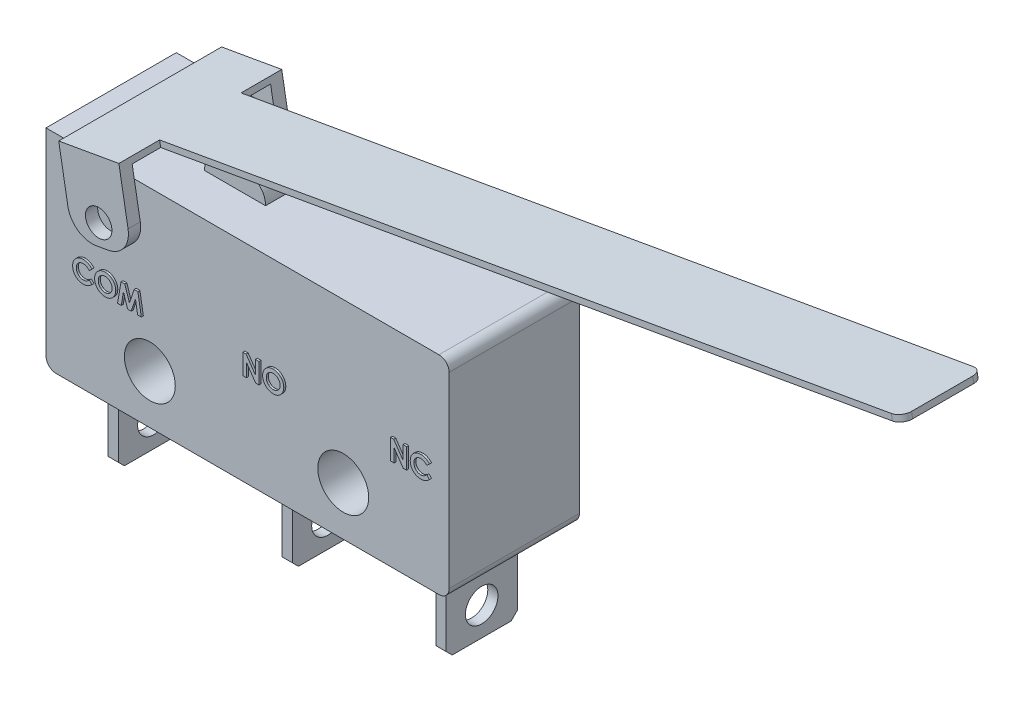
SolidWorks part; units mm, degrees
ref_plane "Front Plane" through (0, 0, 0) normal (0, 0, 1) x (1, 0, 0)
ref_plane "Top Plane" through (0, 0, 0) normal (0, 1, 0) x (1, 0, 0)
ref_plane "Right Plane" through (0, 0, 0) normal (1, 0, 0) x (0, 0, -1)
sketch "Sketch1" plane through (0, 0, 0) normal (0, 0, 1) x (1, 0, 0)
  line L0 (9.65, 5.1) -> (-9.65, 5.1)
  line L1 (10.15, 4.6) -> (10.15, -4.6)
  line L2 (9.65, -5.1) -> (-9.15, -5.1)
  line L3 (-9.65, 5.1) -> (-9.65, -4.6)
  circle A0 centre (-4.55, -2.7) radius 1.25
  circle A1 centre (4.95, -2.7) radius 1.25
  arc A2 (-9.15, -5.1) -> (-9.65, -4.6) centre (-9.15, -4.6) cw
  arc A3 (9.65, 5.1) -> (10.15, 4.6) centre (9.65, 4.6) cw
  arc A4 (10.15, -4.6) -> (9.65, -5.1) centre (9.65, -4.6) cw
  point P2 (0, 5.1)
  point P6 (10.15, 0)
  point P14 (-9.65, -5.1)
  point P17 (10.15, 5.1)
  dimension "D3" = 2.5
  dimension "D4" = 10.2
  dimension "D7" = 2.4
  dimension "D5" = 9.5
  dimension "D6" = 5.1
  dimension "D1" = 2.5
  dimension "D8" = 0.5
  dimension "D2" = 19.8
other "AlignGroup1"
other "AlignGroup2"
extrude "Boss-Extrude2" add sketch "Sketch1" along normal mid plane 6.4
sketch "Sketch2" plane through (0, -5.1, 0) normal (0, -1, 0) x (1, 0, 0)
  line L0 (-9.15, 3.2) -> (-9.15, -3.2) construction
  line L1 (-7.55, 1.75) -> (-8.05, 1.75)
  line L2 (-7.55, 1.75) -> (-7.55, -1.75)
  line L3 (-7.55, -1.75) -> (-8.05, -1.75)
  line L4 (-8.05, 1.75) -> (-8.05, -1.75)
  line L5 (-7.8, -1.75) -> (-7.8, 1.75) construction
  line L6 (-7.55, 0) -> (-8.05, 0) construction
  line L7 (-9.65, 3.2) -> (-9.65, -3.2) construction
  line L9 (1, -1.75) -> (0.5, -1.75)
  line L10 (1, -1.75) -> (1, 1.75)
  line L11 (1, 1.75) -> (0.5, 1.75)
  line L12 (0.5, -1.75) -> (0.5, 1.75)
  line L13 (0.75, 1.75) -> (0.75, -1.75) construction
  line L14 (1, 0) -> (0.5, 0) construction
  line L15 (8.05, -1.75) -> (8.55, -1.75)
  line L16 (8.05, -1.75) -> (8.05, 1.75)
  line L17 (8.05, 1.75) -> (8.55, 1.75)
  line L18 (8.55, -1.75) -> (8.55, 1.75)
  line L19 (8.3, 1.75) -> (8.3, -1.75) construction
  line L20 (8.05, 0) -> (8.55, 0) construction
  point P0 (-7.8, 0)
  point P4 (0.75, 0)
  point P11 (-9.15, 0)
  point P16 (8.3, 0)
  dimension "D1" = 0.5
  dimension "D2" = 3.5
  dimension "D3" = 1.6
  dimension "D4" = 0.5
  dimension "D5" = 3.5
  dimension "D6" = 3.5
  dimension "D7" = 0.5
  dimension "D8" = 8.8
  dimension "D9" = 7.3
extrude "Boss-Extrude3" add sketch "Sketch2" along normal blind 4
chamfer "Chamfer4" distance 0.3 angle 45 6 edges at (8.3, -9.1, 1.75) (8.3, -9.1, -1.75) (0.75, -9.1, 1.75) (0.75, -9.1, -1.75) (-7.8, -9.1, -1.75) (-7.8, -9.1, 1.75)
sketch "Sketch3" plane through (-8.05, 0, 0) normal (-1, 0, 0) x (0, 0, 1)
  line L0 (1.45, -9.1) -> (-1.45, -9.1) construction
  circle A0 centre (0, -7.7) radius 0.8
  point P4 (0, -9.1)
  dimension "D1" = 1.6
  dimension "D2" = 1.4
extrude "Cut-Extrude1" cut sketch "Sketch3" against normal through all
ref_plane "Plane1" through (-1.1631, 6.5965, 0) normal (0.1736, -0.9848, 0) x (0, 0, -1)
sketch "Sketch5" plane through (-1.1631, 6.5965, 0) normal (0.1736, -0.9848, 0) x (0, 0, -1)
  line L0 (-3.2, -8.6178) -> (3.2, -8.6178) construction
  line L1 (2, -7.1178) -> (-2, -7.1178)
  line L2 (2, -7.1178) -> (2, 32.3822)
  line L3 (1.5, 32.8822) -> (-1.5, 32.8822)
  line L4 (-2, -7.1178) -> (-2, 32.3822)
  line L5 (0, 0) -> (0, -8.6178) construction
  line L6 (2, -7.1178) -> (4, -7.1178)
  line L7 (4, -7.1178) -> (4, -4.1178)
  line L8 (2, -4.1178) -> (4, -4.1178)
  line L9 (2, -7.1178) -> (2, -4.1178)
  line L10 (-2, -7.1178) -> (-4, -7.1178)
  line L11 (-2, -7.1178) -> (-2, -4.1178)
  line L12 (-2, -4.1178) -> (-4, -4.1178)
  line L13 (-4, -7.1178) -> (-4, -4.1178)
  arc A0 (2, 32.3822) -> (1.5, 32.8822) centre (1.5, 32.3822) ccw
  arc A1 (-1.5, 32.8822) -> (-2, 32.3822) centre (-1.5, 32.3822) ccw
  point P12 (2, 32.8822)
  point P15 (-2, 32.8822)
  dimension "D3" = 0.5
  dimension "D1" = 4
  dimension "D2" = 40
  dimension "D4" = 1.5
  dimension "D6" = 2
  dimension "D7" = 3
sketch "Sketch7" plane through (0, 5.1, 0) normal (0, 1, 0) x (1, 0, 0)
  line L1 (-0.9455, 0.8808) -> (-3.9455, 0.8808)
  line L2 (-0.9455, 0.8808) -> (-0.9455, -1.1192)
  line L3 (-0.9455, -1.1192) -> (-3.9455, -1.1192)
  line L4 (-3.9455, 0.8808) -> (-3.9455, -1.1192)
  line L5 (-2.4455, -1.1192) -> (-2.4455, 0.8808) construction
  line L6 (-0.9455, -0.1192) -> (-3.9455, -0.1192) construction
  point P0 (-2.4455, -0.1192)
  dimension "D1" = 3
  dimension "D2" = 2
extrude "Boss-Extrude4" add sketch "Sketch7" along normal blind 1 contours L3 L4 L1 L2
fillet "Fillet5" radius 1 2 edges at (-0.9455, 6.1, 0.1192) (-3.9455, 6.1, 0.1192)
extrude "Boss-Extrude6" add sketch "Sketch5" against normal blind 0.3 separate body contours L3 A1 L4 L1 L2 A0 | L2 | L13 L10 L4 L12 region at (11.5102, 8.8311, 0) region at (-6.6956, 5.6209, -3) region at (-6.6956, 5.6209, 3)
sketch "Sketch9" plane through (-1.1631, 6.5965, 0) normal (0.1736, -0.9848, 0) x (0.9848, 0.1736, 0)
  line L0 (-4.1178, 4) -> (-7.1178, 4)
  line L1 (-4.1178, 4) -> (-4.1178, 3.4)
  line L2 (-7.1178, 4) -> (-7.1178, 3.4)
  line L3 (-4.1178, 3.4) -> (-7.1178, 3.4)
  line L8 (-4.8991, 0) -> (-7.1178, 0) construction
  line L9 (-7.1178, -4) -> (-7.1178, 4) construction
  line L10 (-7.1178, -4) -> (-7.1178, -3.4)
  line L11 (-4.1178, -3.4) -> (-7.1178, -3.4)
  line L12 (-4.1178, -4) -> (-7.1178, -4)
  line L13 (-4.1178, -4) -> (-4.1178, -3.4)
  dimension "D1" = 0.6
extrude "Boss-Extrude7" add sketch "Sketch9" along normal blind 3.5
fillet "Fillet6" radius 1.2 4 edges at (-7.565, 1.9136, 3.7) (-4.6106, 2.4346, 3.7) (-4.6106, 2.4346, -3.7) (-7.565, 1.9136, -3.7)
sketch "Sketch13" plane through (0, 0, 4) normal (0, 0, 1) x (1, 0, 0)
  line L1 (-5.7924, 2.2262) -> (-6.3833, 2.122) construction
  line L2 (-8.2249, 5.6559) -> (-7.7734, 3.0954) construction
  circle A0 centre (-6.2615, 3.1589) radius 0.65
  dimension "D1" = 1.3
  dimension "D2" = 1
  dimension "D3" = 1.5
extrude "Cut-Extrude2" cut sketch "Sketch13" against normal up to next (0.6 mm away) contours A0
sketch "Sketch14" plane through (0, 0, -4) normal (0, 0, -1) x (-1, 0, 0)
  line L0 (6.3833, 2.122) -> (5.7924, 2.2262) construction
  line L2 (8.2249, 5.6559) -> (7.7734, 3.0954) construction
  circle A0 centre (6.2615, 3.1589) radius 0.65
  dimension "D1" = 1.3
  dimension "D2" = 1.5
  dimension "D3" = 1
extrude "Cut-Extrude3" cut sketch "Sketch14" against normal up to next (0.6 mm away) contours A0
sketch "Sketch15" plane through (0, 0, 3.2) normal (0, 0, 1) x (1, 0, 0)
  text T0 "COM" font "Century Gothic" height 1
  text T1 "NO\r\n" font "Century Gothic" height 1
  text T2 "NC\r\n" font "Century Gothic" height 1
extrude "Boss-Extrude8" add sketch "Sketch15" along normal blind 0.1
